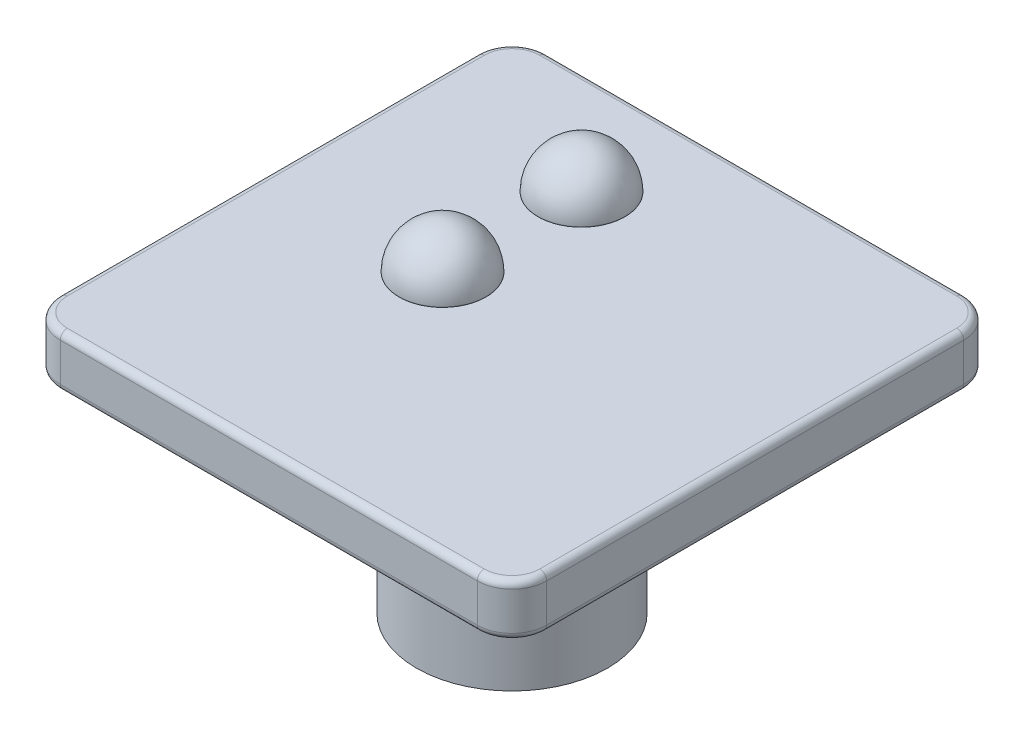
SolidWorks part; units mm, degrees
ref_plane "Front Plane" through (0, 0, 0) normal (0, 0, 1) x (1, 0, 0)
ref_plane "Top Plane" through (0, 0, 0) normal (0, 1, 0) x (1, 0, 0)
ref_plane "Right Plane" through (0, 0, 0) normal (1, 0, 0) x (0, 0, -1)
sketch "Sketch1" plane through (0, 0, 0) normal (0, 1, 0) x (1, 0, 0)
  line L1 (-7.3247, 4.3967) -> (4.6753, 4.3967)
  line L2 (-8.3247, 3.3967) -> (-8.3247, -8.6033)
  line L3 (-7.3247, -9.6033) -> (4.6753, -9.6033)
  line L4 (5.6753, 3.3967) -> (5.6753, -8.6033)
  arc A0 (-8.3247, -8.6033) -> (-7.3247, -9.6033) centre (-7.3247, -8.6033) ccw
  arc A1 (4.6753, -9.6033) -> (5.6753, -8.6033) centre (4.6753, -8.6033) ccw
  arc A2 (4.6753, 4.3967) -> (5.6753, 3.3967) centre (4.6753, 3.3967) cw
  arc A3 (-7.3247, 4.3967) -> (-8.3247, 3.3967) centre (-7.3247, 3.3967) ccw
  point P8 (5.6753, -9.6033)
  point P11 (5.6753, 4.3967)
  point P14 (-8.3247, 4.3967)
  dimension "D3" = 1
  dimension "D1" = 14
  dimension "D2" = 14
extrude "Boss-Extrude1" add sketch "Sketch1" along normal blind 1.5
sketch "Sketch2" plane through (0, 0, 0) normal (0, -1, 0) x (1, 0, 0)
  line L0 (-7.3247, 9.6033) -> (4.6753, 9.6033) construction
  line L1 (5.6753, 8.6033) -> (5.6753, -3.3967) construction
  line L2 (-1.3247, -4.3967) -> (-1.3247, 9.6033) construction
  line L3 (-8.3247, 2.6033) -> (5.6753, 2.6033) construction
  line L4 (-8.3247, -3.3967) -> (-8.3247, 8.6033) construction
  circle A0 centre (-1.3247, 2.6033) radius 2.75
  dimension "D1" = 7
  dimension "D2" = 7
extrude "Boss-Extrude2" add sketch "Sketch2" along normal blind 6
sketch "Sketch3" plane through (0, -6, 0) normal (0, -1, 0) x (1, 0, 0)
  line L0 (-1.3247, 5.3533) -> (-1.3247, -0.1467) construction
  line L1 (-3.3247, 3.1533) -> (0.6753, 3.1533)
  line L2 (-3.3247, 3.1533) -> (-3.3247, 2.0533)
  line L3 (-3.3247, 2.0533) -> (0.6753, 2.0533)
  line L4 (0.6753, 3.1533) -> (0.6753, 2.0533)
  line L5 (-1.8747, 4.6033) -> (-0.7747, 4.6033)
  line L6 (-1.8747, 4.6033) -> (-1.8747, 0.6033)
  line L7 (-1.8747, 0.6033) -> (-0.7747, 0.6033)
  line L8 (-0.7747, 4.6033) -> (-0.7747, 0.6033)
  line L9 (-4.0747, 2.6033) -> (1.4253, 2.6033) construction
  circle A3 centre (-1.3247, 2.6033) radius 2.75 construction
  circle A4 centre (-1.3247, 2.6033) radius 2.75 construction
  dimension "D7" = 0.55
  dimension "D1" = 4
  dimension "D2" = 1.1
  dimension "D3" = 1.1
  dimension "D4" = 4
  dimension "D5" = 2
  dimension "D6" = 2
  dimension "D8" = 0.55
extrude "Cut-Extrude1" cut sketch "Sketch3" against normal blind 6 contours L8 L5 L6 L1 | L1 L8 L3 L4 | L8 L1 L6 L3 | L6 L1 L2 L3 | L8 L3 L6 L7 region at (-2.5997, -6, 2.6033) region at (-1.3247, -6, 3.8783) region at (-1.3247, -6, 2.6033) region at (-0.0497, -6, 2.6033) region at (-1.3247, -6, 1.3283)
chamfer "Chamfer1" distance 0.3 angle 45 12 edges at (-1.3247, -6, 0.6033) (-1.8747, -6, 1.3283) (-2.5997, -6, 2.0533) (-3.3247, -6, 2.6033) (-2.5997, -6, 3.1533) (-0.7747, -6, 1.3283) (-0.0497, -6, 2.0533) (0.6753, -6, 2.6033) (-0.0497, -6, 3.1533) (-0.7747, -6, 3.8783) (-1.3247, -6, 4.6033) (-1.8747, -6, 3.8783)
fillet "Fillet1" radius 1 1 edges at (-1.3247, 0, -0.1467)
sketch "Sketch4" plane through (0, 1.5, 0) normal (0, 1, 0) x (1, 0, 0)
  line L0 (-1.3247, 4.3967) -> (-1.3247, -9.6033) construction
  line L1 (4.6753, 4.3967) -> (-7.3247, 4.3967) construction
  line L2 (-7.3247, -9.6033) -> (4.6753, -9.6033) construction
  line L3 (5.6753, -2.6033) -> (-8.3247, -2.6033) construction
  line L4 (-8.3247, 3.3967) -> (-8.3247, -8.6033) construction
  line L5 (5.6753, -8.6033) -> (5.6753, 3.3967) construction
  line L6 (-3.3247, 4.3967) -> (-3.3247, -9.6033) construction
  line L7 (0.6753, 4.3967) -> (0.6753, -9.6033) construction
  line L8 (-8.3247, 1.3967) -> (5.6753, 1.3967) construction
  line L9 (5.6753, -6.6033) -> (-8.3247, -6.6033) construction
  circle A0 centre (-3.3247, 1.3967) radius 1.25
  circle A2 centre (-3.3247, -2.6033) radius 1.25
  dimension "D1" = 4
  dimension "D2" = 4
  dimension "D3" = 2
  dimension "D4" = 2
extrude "Boss-Extrude3" add sketch "Sketch4" along normal blind 0.01
dome "Dome1" faces to dome 1 distance 1.25 reverse direction no elliptical dome no face at (-3.3247, 1.51, -0.1467) parameters "D1"=1.25
dome "Dome3" faces to dome 1 distance 1.25 reverse direction no elliptical dome no face at (-3.3247, 1.51, 3.8533) parameters "D1"=1.25
fillet "Fillet3" radius 0.2 16 edges at (5.3824, 1.5, -4.1038) (5.6753, 1.5, 2.6033) (5.3824, 1.5, 9.3104) (-1.3247, 1.5, 9.6033) (-8.0318, 1.5, 9.3104) (-8.0318, 1.5, -4.1038) (-8.3247, 1.5, 2.6033) (-1.3247, 1.5, -4.3967) (5.3824, 0, 9.3104) (5.6753, 0, 2.6033) (5.3824, 0, -4.1038) (-1.3247, 0, -4.3967) (-8.0318, 0, -4.1038) (-8.3247, 0, 2.6033) (-8.0318, 0, 9.3104) (-1.3247, 0, 9.6033)
